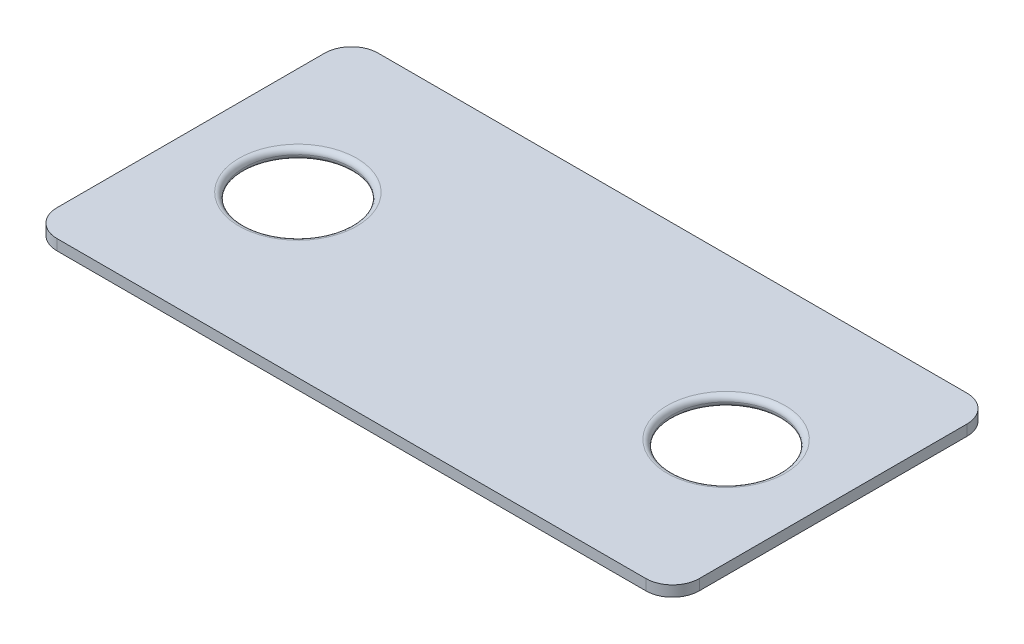
SolidWorks part; units mm, degrees
ref_plane "Front Plane" through (0, 0, 0) normal (0, 0, 1) x (1, 0, 0)
ref_plane "Top Plane" through (0, 0, 0) normal (0, 1, 0) x (1, 0, 0)
ref_plane "Right Plane" through (0, 0, 0) normal (1, 0, 0) x (0, 0, -1)
sketch "Sketch1" plane through (0, 0, 0) normal (0, 1, 0) x (1, 0, 0)
  line L1 (55, -30) -> (-55, -30)
  line L2 (60, -25) -> (60, 25)
  line L3 (55, 30) -> (-55, 30)
  line L4 (-60, -25) -> (-60, 25)
  line L5 (60, -30) -> (-60, 30) construction
  line L6 (60, 30) -> (-60, -30) construction
  circle A0 centre (-40, 0) radius 10
  circle A1 centre (40, 0) radius 10
  arc A2 (-55, -30) -> (-60, -25) centre (-55, -25) cw
  arc A3 (60, 25) -> (55, 30) centre (55, 25) ccw
  arc A4 (55, -30) -> (60, -25) centre (55, -25) ccw
  arc A5 (-55, 30) -> (-60, 25) centre (-55, 25) ccw
  point P0 (0, 0)
  dimension "D1" = 20
  dimension "D8" = 5
  dimension "D2" = 120
  dimension "D3" = 60
  dimension "D4" = 20
  dimension "D5" = 20
  dimension "D6" = 30
  dimension "D7" = 40
base flange "Base-Flange1" sketch "Sketch1" thickness 2 reverse thickness direction no parameters "D1"=0.7366
fillet "Fillet1" radius 1 2 edges at (40, 0, 10) (-40, 0, 10)
fillet "Fillet2" radius 1 1 edges at (-40, -2, 10)
fillet "Fillet3" radius 1 1 edges at (40, -2, 10)
sketch "Bend-Lines1" [suppressed] plane through (0, 0, 0) normal (0, 1, 0) x (1, 0, 0)
sketch "Bounding-Box1" [suppressed] plane through (0, 0, 0) normal (0, 1, 0) x (1, 0, 0)
sheet metal parameters "Sheet-Metal1" thickness 2 parameters "D1"=0.7366
flat pattern "Flat-Pattern1" [suppressed]
sketch "Bend-Lines2" plane through (0, 0, 0) normal (0, 1, 0) x (1, 0, 0)
sketch3d "Bounding-Box2" [suppressed]
  line L0 (-5, 54.9999, 0) -> (115, 55, 0) construction
  line L1 (-5, -5, 0) -> (115, -4.9999, 0) construction
  line L2 (-5, 54.9999, 0) -> (-5, -5, 0) construction
  line L3 (115, 55, 0) -> (115, -4.9999, 0) construction
